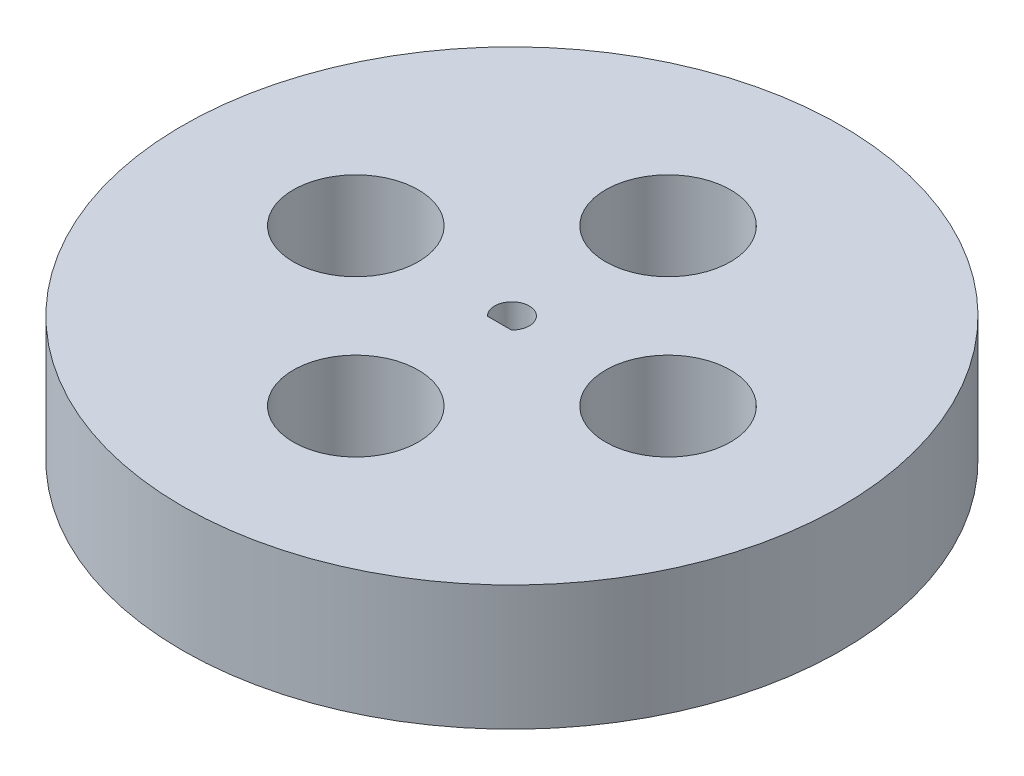
SolidWorks part; units mm, degrees
ref_plane "Front Plane" through (0, 0, 0) normal (0, 0, 1) x (1, 0, 0)
ref_plane "Top Plane" through (0, 0, 0) normal (0, 1, 0) x (1, 0, 0)
ref_plane "Right Plane" through (0, 0, 0) normal (1, 0, 0) x (0, 0, -1)
sketch "Sketch1" plane through (0, 0, 0) normal (0, 1, 0) x (1, 0, 0)
  line L0 (0, 2.7713) -> (0, -2)
  line L1 (-1.9183, -2) -> (1.9183, -2)
  arc A0 (1.9183, -2) -> (-1.9183, -2) centre (0, 0) ccw
  circle A1 centre (0, 0) radius 52.7713
  circle A2 centre (0, 0) radius 2.7713 construction
  circle A3 centre (0, 0) radius 10
  point P10 (0, -2)
  dimension "D1" = 50
  dimension "D2" = 2
extrude "Boss-Extrude1" add sketch "Sketch1" along normal blind 20 contours L1 A0 L0 | L0 A0 L1 | A1 region at (1.2168, 0, -0.213) region at (-1.2168, 0, -0.213)
sketch "Sketch2" plane through (0, 20, 0) normal (0, 1, 0) x (1, 0, 0)
  circle A0 centre (0, 0) radius 25
sketch "Sketch3" plane through (0, 20, 0) normal (0, 1, 0) x (1, 0, 0)
  line L0 (0, 25) -> (0, -25) construction
  line L1 (-25, 0) -> (25, 0) construction
  circle A0 centre (0, 0) radius 25 construction
  circle A1 centre (-25, 0) radius 10
  circle A2 centre (0, 25) radius 10
  circle A3 centre (25, 0) radius 10
  circle A4 centre (0, -25) radius 10
  point P8 (0, 0)
  point P12 (0, 0)
  point P19 (0, 0)
  dimension "D1" = 4
extrude "Cut-Extrude1" cut sketch "Sketch3" against normal blind 20
